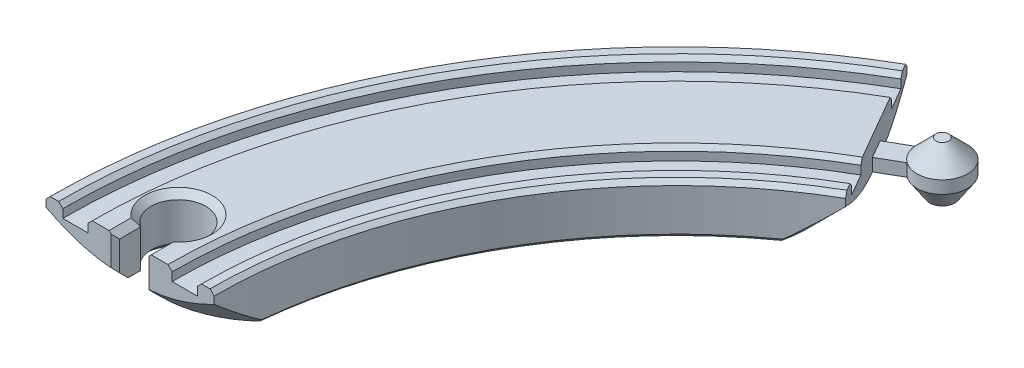
SolidWorks part; units mm, degrees
note: The reader was unsure of these and kept them because the rebuilt part matched: shared geometry of "Sketch4<3>", "Sketch4<5>".
ref_plane "Front Plane" through (0, 0, 0) normal (0, 0, 1) x (1, 0, 0)
ref_plane "Top Plane" through (0, 0, 0) normal (0, 1, 0) x (1, 0, 0)
ref_plane "Right Plane" through (0, 0, 0) normal (1, 0, 0) x (0, 0, -1)
sketch "Sketch2" plane through (0, 0, 0) normal (0, 0, 1) x (1, 0, 0)
  line L0 (-20, 0) -> (20, 0)
  line L1 (20, 0) -> (20, 12)
  line L2 (20, 12) -> (16, 12)
  line L3 (16, 12) -> (16, 9)
  line L4 (16, 9) -> (10, 9)
  line L5 (10, 9) -> (10, 12)
  line L6 (10, 12) -> (-10, 12)
  line L7 (-10, 12) -> (-10, 9)
  line L8 (-10, 9) -> (-16, 9)
  line L9 (-16, 9) -> (-16, 12)
  line L10 (-16, 12) -> (-20, 12)
  line L11 (-20, 12) -> (-20, 0)
  line L12 (129.9038, 0) -> (129.9038, 12)
  point P4 (0, 0)
  dimension "D1" = 40
  dimension "D2" = 12
  dimension "D3" = 3
  dimension "D4" = 4
  dimension "D5" = 6
  dimension "D6" = 129.9038
revolve "Revolve1" add sketch "Sketch2" angle 60 about L12
sketch "Sketch3" plane through (0, 12, 0) normal (0, 1, 0) x (1, 0, 0)
  line L0 (10, 0) -> (-10, 0) construction
  line L2 (-3.5, 0) -> (3.5, 0)
  line L3 (-3.5, 0) -> (-3.5, 11.5)
  line L4 (-3.5, 11.5) -> (3.5, 11.5)
  line L5 (3.5, 0) -> (3.5, 11.5)
  line L6 (-3.5, 0) -> (3.5, 11.5) construction
  line L7 (-3.5, 11.5) -> (3.5, 0) construction
  circle A0 centre (0, 11.5) radius 6.5
  point P4 (0, 5.75)
  point P10 (0, 0)
  line M6 (-10, 0) -> (10, 0)
  dimension "D1" = 13
  dimension "D2" = 11.5
  dimension "D3" = 7
extrude "Cut-Extrude1" cut sketch "Sketch3" against normal through all contours L5 A0 L3 L4 | L3 A0 L5 L4 | A0 L3 L5 M6
sketch "Sketch4" plane through (0, 12, 0) normal (0, 1, 0) x (1, 0, 0)
  line L0 (66.2019, 110.3349) -> (63.7019, 114.6651)
  line L1 (66.2019, 110.3349) -> (76.1612, 116.0849)
  line L2 (63.7019, 114.6651) -> (73.6612, 120.4151)
  line L3 (76.1612, 116.0849) -> (73.6612, 120.4151)
  line L4 (69.9519, 103.8397) -> (59.9519, 121.1603) construction
  circle A0 centre (74.9112, 118.25) radius 6
  point P9 (64.9519, 112.5)
  line M6 (69.9519, 103.8397) -> (59.9519, 121.1603)
  dimension "D1" = 12
  dimension "D2" = 5
  dimension "D3" = 11.5
extrude "Boss-Extrude1" add sketch "Sketch4" against normal up to surface (12 mm away) contours L1 A0 L2 L3 | L2 A0 L1 L3 up to face at (12.4699, 0, -33.3033)
extrude "Boss-Extrude2" add sketch "Sketch4<3>" against normal blind 7.5 contours A0 L2 L1 M6
sketch "Sketch4<3>" plane through (0, 12, 0) normal (0, 1, 0) x (1, 0, 0) same geometry as "Sketch4"
extrude "Cut-Extrude2" cut sketch "Sketch4<5>" against normal blind 4.5 contours A0 L2 L1 M6
sketch "Sketch4<5>" plane through (0, 12, 0) normal (0, 1, 0) x (1, 0, 0) same geometry as "Sketch4"
chamfer "Chamfer2" distance 4.5 angle 45 1 edges at (68.9112, 12, -118.25)
chamfer "Chamfer5" distance 3 distance2 4.5 1 edges at (74.9112, 0, -124.25)
chamfer "Chamfer3" distance 1.5 angle 45 6 edges at (0, 0, -18) (3.5, 0, -3.0114) (-3.5, 12, -3.0114) (-3.5, 0, -3.0114) (0, 12, -18) (3.5, 12, -3.0114)
sketch "Sketch17" plane through (-33.726, 0, -58.4151) normal (-0.5, 0, -0.866) x (-0.866, 0, 0.5)
  line L0 (-118.5456, 10.5456) -> (-118.5456, 0)
  line L1 (-118.5456, 0) -> (-108, 0)
  line L2 (-108, 0) -> (-118.5456, 10.5456)
  line L4 (-83, -1.2652) -> (-83, 10.5456) construction
  dimension "D1" = 25
revolve "Cut-Revolve1" cut sketch "Sketch17" angle 90 about L4
ref_plane "Plane1" through (-32.476, 0, -56.25) normal (-0.5, 0, -0.866) x (-0.866, 0, 0.5)
mirror "Mirror1" about plane through (-32.476, 0, -56.25) normal (-0.5, 0, -0.866) of "Cut-Revolve1"
chamfer "Chamfer4" distance 4.5 angle 45 1 edges at (64.9519, 0, -112.5)
ref_plane "Plane2" through (32.476, 0, -56.25) normal (0.5, 0, -0.866) x (-0.866, 0, -0.5)
mirror "Mirror4" about plane through (32.476, 0, -56.25) normal (0.5, 0, -0.866) of "Cut-Revolve1", "Mirror1"
chamfer "Chamfer1" distance 1 angle 45 15 edges at (0.0833, 0, -74.9519) (34.7243, 0, -54.9519) (-3.5, 7.5085, 0) (3.5, 7.5085, 0) (3.5474, 12, -72.9519) (8.7436, 12, -69.9519) (26.0641, 12, -59.9519) (31.2602, 12, -56.9519) (34.7243, 12, -54.9519) (0.0833, 12, -74.9519)
